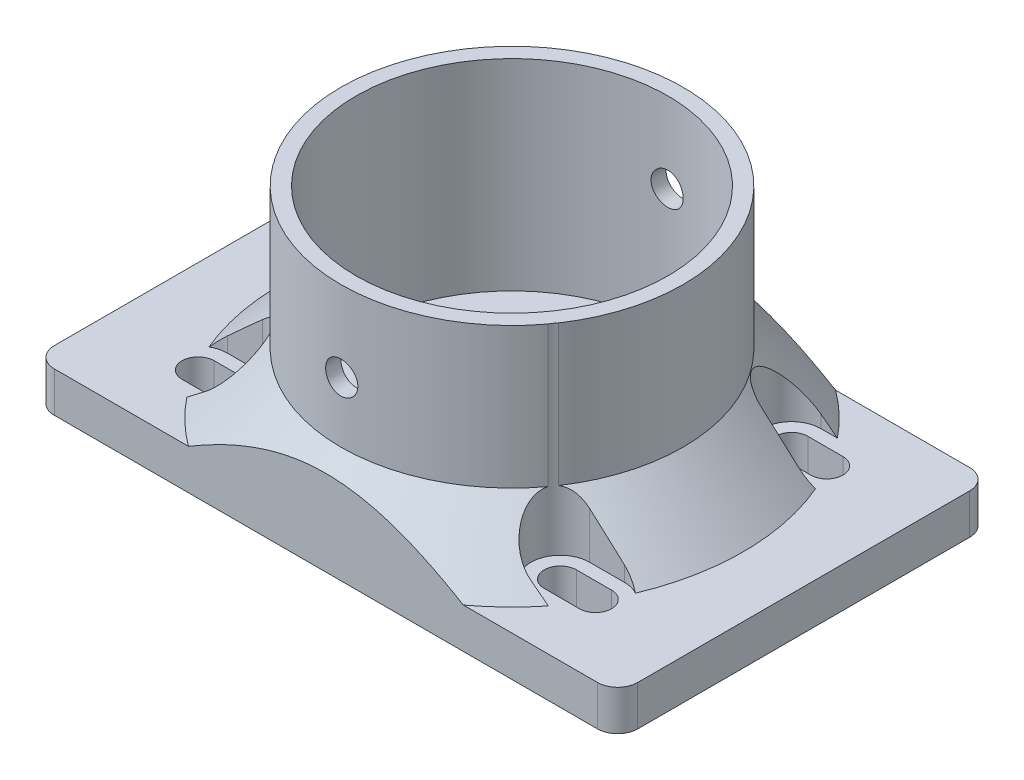
SolidWorks part; units mm, degrees
material "PET"
ref_plane "Спереди" through (0, 0, 0) normal (0, 0, 1) x (1, 0, 0)
ref_plane "Сверху" through (0, 0, 0) normal (0, 1, 0) x (1, 0, 0)
ref_plane "Справа" through (0, 0, 0) normal (1, 0, 0) x (0, 0, -1)
sketch "Эскиз1" plane through (0, 0, 0) normal (0, 1, 0) x (1, 0, 0)
  line L0 (0, 0) -> (-64.6711, 0) construction
  line L1 (27, 18.5) -> (-27, 18.5)
  line L2 (29, 16.5) -> (29, -16.5)
  line L3 (27, -18.5) -> (-27, -18.5)
  line L4 (-29, 16.5) -> (-29, -16.5)
  line L5 (0, 0) -> (0, 30.1257) construction
  line L6 (-19.75, -11.4506) -> (-16.25, -11.4506) construction
  line L7 (-19.75, -9.8506) -> (-16.25, -9.8506)
  line L8 (-19.75, -13.0506) -> (-16.25, -13.0506)
  line L9 (-22.4938, 11.45) -> (-15.3671, 11.45)
  line L10 (18, -9.8506) -> (18, -15.2919)
  line L11 (16.25, -11.4506) -> (19.75, -11.4506) construction
  line L12 (16.25, -9.8506) -> (19.75, -9.8506)
  line L13 (16.25, -13.0506) -> (19.75, -13.0506)
  line L14 (16.25, 11.5494) -> (19.75, 11.5494) construction
  line L15 (16.25, 13.1494) -> (19.75, 13.1494)
  line L16 (16.25, 9.9494) -> (19.75, 9.9494)
  line L17 (-19.75, 11.5494) -> (-16.25, 11.5494) construction
  line L18 (-19.75, 13.1494) -> (-16.25, 13.1494)
  line L19 (-19.75, 9.9494) -> (-16.25, 9.9494)
  arc A4 (29, -16.5) -> (27, -18.5) centre (27, -16.5) cw
  arc A5 (27, 18.5) -> (29, 16.5) centre (27, 16.5) cw
  arc A6 (-27, 18.5) -> (-29, 16.5) centre (-27, 16.5) ccw
  arc A7 (-29, -16.5) -> (-27, -18.5) centre (-27, -16.5) ccw
  arc A8 (-19.75, -9.8506) -> (-19.75, -13.0506) centre (-19.75, -11.4506) ccw
  arc A9 (-16.25, -13.0506) -> (-16.25, -9.8506) centre (-16.25, -11.4506) ccw
  arc A10 (16.25, -9.8506) -> (16.25, -13.0506) centre (16.25, -11.4506) ccw
  arc A11 (19.75, -13.0506) -> (19.75, -9.8506) centre (19.75, -11.4506) ccw
  arc A12 (16.25, 13.1494) -> (16.25, 9.9494) centre (16.25, 11.5494) ccw
  arc A13 (19.75, 9.9494) -> (19.75, 13.1494) centre (19.75, 11.5494) ccw
  arc A14 (-19.75, 13.1494) -> (-19.75, 9.9494) centre (-19.75, 11.5494) ccw
  arc A15 (-16.25, 9.9494) -> (-16.25, 13.1494) centre (-16.25, 11.5494) ccw
  point P0 (0, 0)
  point P19 (-18, -11.4506)
  point P23 (29, -18.5)
  point P26 (29, 18.5)
  point P31 (-29, -18.5)
  point P36 (18, -11.4506)
  point P43 (18, 11.5494)
  point P50 (-18, 11.5494)
  dimension "D3" = 3.2
  dimension "D4" = 7.05
  dimension "D7" = 2
  dimension "D1" = 58
  dimension "D2" = 37
  dimension "D5" = 11
  dimension "D6" = 2
  dimension "D8" = 3.5
  dimension "D9" = 2
extrude "Бобышка-Вытянуть1" add sketch "Эскиз1" along normal blind 4 contours L4 A7 L3 A4 L2 A5 L1 A6 A15 L19 A14 L18 A13 L16 A12 L15 A11 L13 A10 L12 A9 L8 A8 L7 region at (0, 0, 0.0018)
sketch "Эскиз2" plane through (0, 4, 0) normal (0, 1, 0) x (1, 0, 0)
  circle A0 centre (0, 0) radius 15.5
  circle A1 centre (0, 0) radius 17
  dimension "D1" = 31
  dimension "D2" = 34
extrude "Бобышка-Вытянуть2" add sketch "Эскиз2" along normal blind 20
sketch "Эскиз3" plane through (0, 0, 0) normal (0, 0, 1) x (1, 0, 0)
  circle A0 centre (0, 16) radius 1.6
  dimension "D2" = 3.2
  dimension "D1" = 16
extrude "Вырез-Вытянуть1" cut sketch "Эскиз3" against normal through all both and the other way through all
chamfer "Фаска1" distance 6 angle 45 1 edges at (0, 4, 17)
sketch "Эскиз4" plane through (0, 4, 0) normal (0, 1, 0) x (1, 0, 0)
  line L0 (-19.75, 11.5494) -> (-16.25, 11.5494) construction
  line L1 (-19.75, 14.4554) -> (-16.25, 14.4554)
  line L2 (-19.75, 8.6435) -> (-16.25, 8.6435)
  line L3 (16.25, 11.5494) -> (19.75, 11.5494) construction
  line L4 (16.25, 14.4554) -> (19.75, 14.4554)
  line L5 (16.25, 8.6435) -> (19.75, 8.6435)
  line L6 (16.25, -11.4506) -> (19.75, -11.4506) construction
  line L7 (16.25, -8.5446) -> (19.75, -8.5446)
  line L8 (16.25, -14.3565) -> (19.75, -14.3565)
  line L9 (-19.75, -11.4506) -> (-16.25, -11.4506) construction
  line L10 (-19.75, -8.5446) -> (-16.25, -8.5446)
  line L11 (-19.75, -14.3565) -> (-16.25, -14.3565)
  arc A0 (-19.75, 14.4554) -> (-19.75, 8.6435) centre (-19.75, 11.5494) ccw
  arc A1 (-16.25, 8.6435) -> (-16.25, 14.4554) centre (-16.25, 11.5494) ccw
  arc A2 (16.25, 14.4554) -> (16.25, 8.6435) centre (16.25, 11.5494) ccw
  arc A3 (19.75, 8.6435) -> (19.75, 14.4554) centre (19.75, 11.5494) ccw
  arc A4 (16.25, -8.5446) -> (16.25, -14.3565) centre (16.25, -11.4506) ccw
  arc A5 (19.75, -14.3565) -> (19.75, -8.5446) centre (19.75, -11.4506) ccw
  arc A6 (-19.75, -8.5446) -> (-19.75, -14.3565) centre (-19.75, -11.4506) ccw
  arc A7 (-16.25, -14.3565) -> (-16.25, -8.5446) centre (-16.25, -11.4506) ccw
  point P6 (-18, 11.5494)
  point P16 (18, 11.5494)
  point P23 (18, -11.4506)
  point P30 (-18, -11.4506)
  dimension "D1" = 2
  dimension "D2" = 2
extrude "Вырез-Вытянуть2" cut sketch "Эскиз4" along normal blind 20
